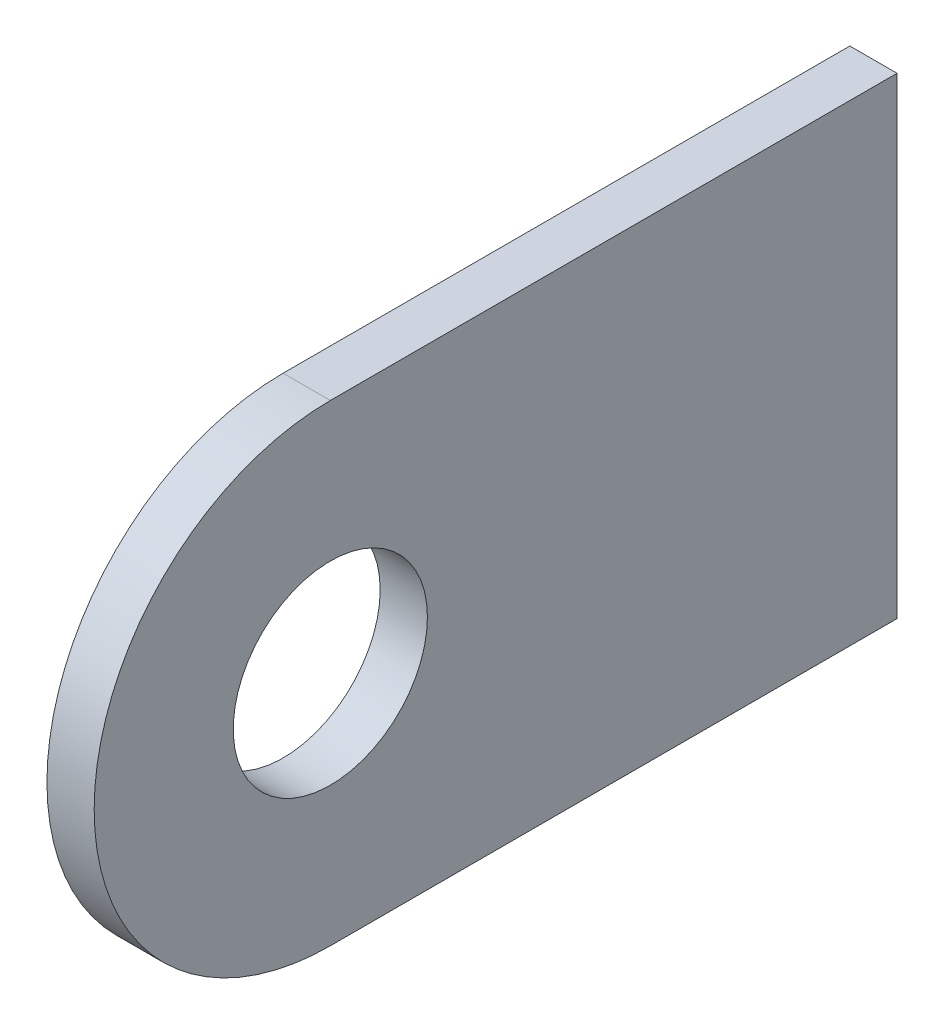
SolidWorks part; units mm, degrees
material "AISI 4130 Steel, annealed at 865C"
ref_plane "X-Y Datum" through (0, 0, 0) normal (0, 0, 1) x (1, 0, 0)
ref_plane "X-Z Datum" through (0, 0, 0) normal (0, 1, 0) x (1, 0, 0)
ref_plane "Y-Z Datum" through (0, 0, 0) normal (1, 0, 0) x (0, 0, -1)
sketch "Sketch1" plane through (0, 0, 0) normal (1, 0, 0) x (0, 0, -1)
  line L0 (3.175, -7.9375) -> (3.175, 7.9375)
  line L4 (-15.875, -7.9375) -> (3.175, -7.9375)
  line L5 (-15.875, 7.9375) -> (3.175, 7.9375)
  arc A1 (-15.875, -7.9375) -> (-15.875, 7.9375) centre (-15.875, 0) cw
  point P4 (3.175, 0)
  dimension "D1" = 19.05
  dimension "D2" = 7.9375
  dimension "D3" = 3.175
extrude "Boss-Extrude1" add sketch "Sketch1" along normal blind 1.5875
hole_wizard "1/4 Clearance Hole1" positions "Sketch2" profile "Sketch3" hole size "1/4" standard "ANSI Inch" end condition through all
sketch "Sketch2" plane through (1.5875, 0, 0) normal (1, 0, 0) x (0, 0, -1)
  point P0 (-15.875, 0)
sketch "Sketch3" plane through (1.5875, 0, 15.875) normal (0, 1, 0) x (0, 0, -1)
  line L0 (0, 0) -> (0, 1.5875)
  line L1 (0, 1.5875) -> (3.2639, 1.5875)
  line L2 (3.2639, 1.5875) -> (3.2639, 0)
  line L5 (3.2639, 0) -> (0, 0)
  line L11 (0, -6.35) -> (0, 107.95) construction
  dimension "Thru Hole Dia." = 6.5278
  dimension "Thru Hole Depth" = 1.5875
